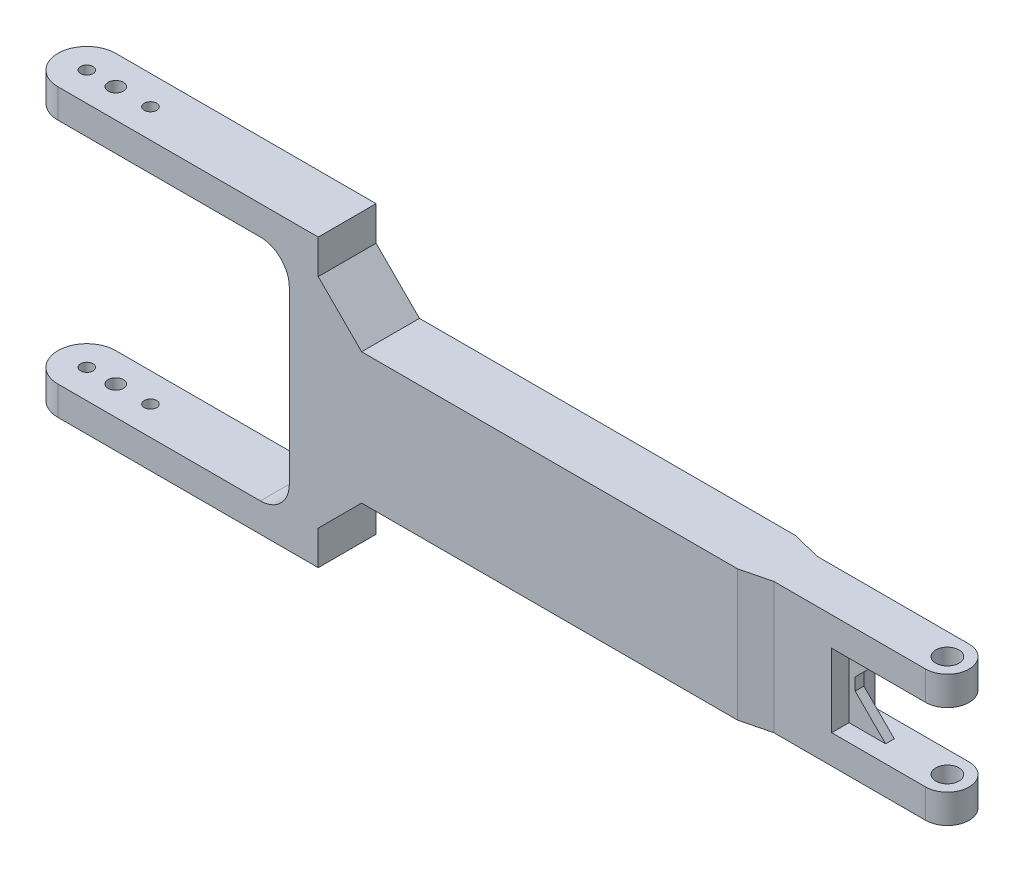
SolidWorks part; units mm, degrees
ref_plane "前视基准面" through (0, 0, 0) normal (0, 0, 1) x (1, 0, 0)
ref_plane "上视基准面" through (0, 0, 0) normal (0, 1, 0) x (1, 0, 0)
ref_plane "右视基准面" through (0, 0, 0) normal (1, 0, 0) x (0, 0, -1)
other "Configuration Table"
sketch "草图2" plane through (0, 0, 0) normal (0, 0, 1) x (1, 0, 0)
  line L0 (0, 12.65) -> (0, -12.65)
  line L1 (0, 12.65) -> (40, 12.65)
  line L2 (40, 12.65) -> (40, 22.65)
  line L3 (40, 22.65) -> (-10, 22.65)
  line L4 (-10, 22.65) -> (-10, -22.65)
  line L5 (-10, -22.65) -> (40, -22.65)
  line L6 (40, -22.65) -> (40, -12.65)
  line L7 (40, -12.65) -> (0, -12.65)
  line L8 (-185, -39.5) -> (-185, 39.5)
  line L9 (-185, -39.5) -> (-275, -39.5)
  line L10 (-275, -39.5) -> (-275, -49.5)
  line L11 (-275, -49.5) -> (-175, -49.5)
  line L12 (-175, -49.5) -> (-175, 49.5)
  line L13 (-175, 49.5) -> (-275, 49.5)
  line L14 (-275, 49.5) -> (-275, 39.5)
  line L15 (-275, 39.5) -> (-185, 39.5)
  line L16 (-10, 22.65) -> (-175, 22.65)
  line L17 (-10, -22.65) -> (-175, -22.65)
  line L18 (0, 0) -> (12.65, 12.65)
  line L19 (0, 0) -> (12.65, -12.65)
  point P4 (0, 0)
  point P12 (-185, 0)
  point P21 (0, 0)
  dimension "D1" = 25.3
  dimension "D2" = 40
  dimension "D3" = 10
  dimension "D4" = 10
  dimension "D5" = 79
  dimension "D6" = 90
  dimension "D7" = 10
  dimension "D8" = 10
  dimension "D9" = 10
  dimension "D10" = 165
  dimension "D11" = 45
extrude "凸台-拉伸1" add sketch "草图2" along normal mid plane 20 contours L17 L4 L16 L12 | L14 L15 L8 L9 L10 L11 L12 L13 region at (-92.5, 0, 0) region at (-176.4072, 0, 0)
extrude "凸台-拉伸2" add sketch "草图2<3>" along normal mid plane 15 contours L6 L7 L0 L1 L2 L3 L4 L5 region at (-0.6747, 6.325, 0)
sketch "草图2<3>" plane through (0, 0, 0) normal (0, 0, 1) x (1, 0, 0) same geometry as "草图2"
chamfer "倒角1" distance 20 distance2 5 1 edges at (-10, 0, 10) first distance on face at (-182.5, 0, 10)
chamfer "倒角2" distance 5 distance2 20 1 edges at (-10, 0, -10) first distance on face at (-10, 0, -8.75)
extrude "凸台-拉伸3" add sketch "草图2<5>" along normal mid plane 3 contours L0 L18 L1 | L19 L0 L7 region at (4.2167, 8.4333, 0) region at (4.2167, -8.4333, 0)
sketch "草图2<5>" plane through (0, 0, 0) normal (0, 0, 1) x (1, 0, 0) same geometry as "草图2"
chamfer "倒角3" distance 3 angle 45 1 edges at (0, 0, 0)
sketch "草图3" plane through (0, 49.5, 0) normal (0, 1, 0) x (1, 0, 0)
  line L0 (-275, 0) -> (-175, 0) construction
  line L4 (-175, 10) -> (-275, 10)
  line L5 (-275, 10) -> (-275, -10)
  line L6 (-275, -10) -> (-175, -10)
  line L7 (-175, -10) -> (-175, 10)
  line L8 (-175, 10) -> (-275, 10)
  line L9 (-275, 10) -> (-275, -10)
  line L10 (-275, -10) -> (-175, -10)
  line L11 (-175, -10) -> (-175, 10)
  circle A0 centre (-255, 0) radius 2.65
  circle A1 centre (-265, 0) radius 2.15
  circle A2 centre (-243, 0) radius 2.15
  arc A3 (-265, 10) -> (-265, -10) centre (-265, 0) ccw
  point P10 (-263.5697, 0)
  point P16 (0, 0)
  point P17 (-264.85, 0)
  point P18 (0, 0)
  point P19 (0, 0)
  point P20 (0, 0)
  line M6 (-275, 10) -> (-275, -10)
  line M7 (-275, -10) -> (-175, -10)
  dimension "D2" = 5.3
  dimension "D5" = 4.3
  dimension "D7" = 180
  dimension "D3" = 10
  dimension "D4" = 12
  dimension "D6" = 80
  dimension "D1" = 0
extrude "切除-拉伸1" cut sketch "草图3" against normal through all contours A3 L8 M6 | A3 L9 M7 | L0 A1 | A1 L0 | A0 L0 | L0 A0 | A2 L0 | L0 A2 region at (-243, 49.5, 0.9125) region at (-243, 49.5, -0.9125) region at (-255, 49.5, 1.1247) region at (-255, 49.5, -1.1247) region at (-272.7663, 49.5, 7.7663) region at (-272.7663, 49.5, -7.7663) region at (-265, 49.5, 0.9125) region at (-265, 49.5, -0.9125)
sketch "草图4" plane through (0, 22.65, 0) normal (0, 1, 0) x (1, 0, 0)
  line L0 (0, 0) -> (40, 0) construction
  line L1 (40, -7.5) -> (40, 7.5) construction
  line L8 (40, 7.5) -> (-20, 7.5)
  line L9 (-20, 7.5) -> (-30, 10)
  line L10 (-30, 10) -> (-175, 10)
  line L11 (-175, 10) -> (-175, -10)
  line L12 (-175, -10) -> (-30, -10)
  line L13 (-30, -10) -> (-20, -7.5)
  line L14 (-20, -7.5) -> (40, -7.5)
  line L15 (40, -7.5) -> (40, 7.5)
  line L16 (40, 7.5) -> (-20, 7.5)
  line L17 (-20, 7.5) -> (-30, 10)
  line L18 (-30, 10) -> (-175, 10)
  line L19 (-175, 10) -> (-175, -10)
  line L20 (-175, -10) -> (-30, -10)
  line L21 (-30, -10) -> (-20, -7.5)
  line L22 (-20, -7.5) -> (40, -7.5)
  line L23 (40, -7.5) -> (40, 7.5)
  circle A0 centre (32.5, 0) radius 7.5
  circle A1 centre (32.5, 0) radius 4
  point P12 (40, 0)
  point P16 (0, 0)
  point P18 (34.3626, 0)
  line M10 (40, 7.5) -> (-20, 7.5)
  line M17 (40, -7.5) -> (40, 7.5)
  dimension "D2" = 8
  dimension "D1" = 0
extrude "切除-拉伸2" cut sketch "草图4" against normal through all contours A1 L0 | L0 A1 | A0 L23 M10 | A0 L22 M17 region at (32.5, 22.65, 1.6977) region at (32.5, 22.65, -1.6977) region at (38.3247, 22.65, -5.8247) region at (38.3247, 22.65, 5.8247)
chamfer "倒角4" distance 15 angle 45 2 edges at (-175, -22.65, 0) (-175, 22.65, 0)
fillet "圆角1" radius 10 2 edges at (-185, 39.5, 0) (-185, -39.5, 0)
